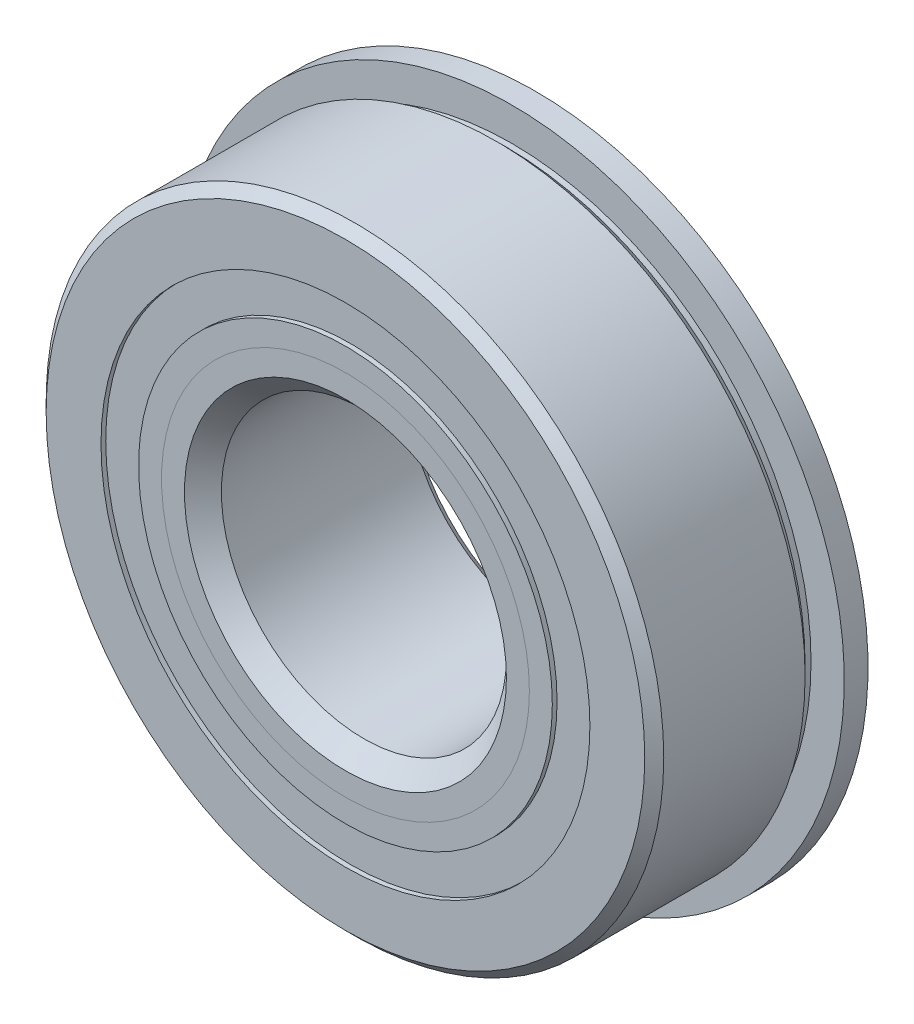
SolidWorks part; units mm, degrees
ref_plane "Front Plane" through (0, 0, 0) normal (0, 0, 1) x (1, 0, 0)
ref_plane "Top Plane" through (0, 0, 0) normal (0, 1, 0) x (1, 0, 0)
ref_plane "Right Plane" through (0, 0, 0) normal (1, 0, 0) x (0, 0, -1)
sketch "Sketch1" plane through (0, 0, 0) normal (1, 0, 0) x (0, 0, -1)
  line L0 (-6.35, 0) -> (6.35, 0) construction
  line L1 (0, 20.6375) -> (0, -20.6375) construction
  line L2 (5.715, 20.6375) -> (-5.715, 20.6375)
  line L3 (-5.715, 20.6375) -> (-6.35, 20.0025)
  line L4 (-6.35, 20.0025) -> (-6.35, 16.3373)
  line L5 (-6.35, 16.3373) -> (-2.8222, 16.3373)
  line L6 (6.35, 16.3373) -> (2.8222, 16.3373)
  line L7 (6.35, 20.0025) -> (6.35, 16.3373)
  line L8 (5.715, 20.6375) -> (6.35, 20.0025)
  line L9 (0, 20.6375) -> (0, 15.0813) construction
  line L10 (0, 15.0813) -> (0, 9.525) construction
  line L11 (6.35, 0) -> (7.9375, 0) construction
  arc A0 (-2.8222, 16.3373) -> (2.8222, 16.3373) centre (0, 15.0813) cw
  point P14 (0, 9.525)
  dimension "D3" = 5.6444
  dimension "D1" = 45
  dimension "Width" = 12.7
  dimension "OD" = 41.275
  dimension "D2" = 0.635
  dimension "Shaft Dia" = 19.05
  dimension "D4" = 1.256
  dimension "Total Wd" = 14.2875
revolve "Revolve1" add sketch "Sketch1" angle 360 about L0
sketch "Sketch2" plane through (0, 0, 0) normal (1, 0, 0) x (0, 0, -1)
  line L0 (-6.35, 13.8252) -> (-2.8222, 13.8252)
  line L1 (-6.35, 20.0025) -> (-6.35, -20.0025) construction
  line L2 (-6.35, 13.8252) -> (-6.35, 12.2919)
  line L3 (-6.35, 12.2919) -> (-4.8167, 10.7586)
  line L4 (-4.8167, 10.7586) -> (0, 10.7586)
  line L5 (0, 20.6375) -> (0, -20.6375) construction
  line L6 (0, 10.7586) -> (0, 11.9921)
  line L7 (0, 11.9921) -> (0, 9.525) construction
  line L8 (-6.35, 13.8252) -> (-6.35, 10.7586) construction
  line L9 (-6.35, 10.7586) -> (-4.8167, 10.7586) construction
  arc A0 (-2.8222, 13.8252) -> (0, 11.9921) centre (0, 15.0813) ccw
  arc A1 (2.8222, 16.3373) -> (-2.8222, 16.3373) centre (0, 15.0813) ccw construction
  circle A2 centre (0, 15.0813) radius 3.0891 construction
  dimension "D1" = 45
revolve "Revolve2" add sketch "Sketch2" angle 360 about L0
sketch "Sketch3" plane through (0, 0, 0) normal (1, 0, 0) x (0, 0, -1)
  line L0 (-6.35, 12.2919) -> (-4.8167, 10.7586)
  line L1 (-4.8167, 10.7586) -> (0, 10.7586)
  line L2 (0, 10.7586) -> (0, 11.9921)
  line L3 (-6.35, 12.2919) -> (-6.35, 10.7586)
  line L4 (-6.35, 13.8252) -> (-6.35, 10.7586) construction
  line L5 (-6.35, 10.7586) -> (-5.1164, 9.525)
  line L6 (-5.1164, 9.525) -> (7.3025, 9.525)
  line L8 (7.3025, 9.525) -> (7.9375, 10.16)
  line L10 (7.9375, 10.16) -> (7.9375, 13.8252)
  line L11 (7.9375, 13.8252) -> (2.8222, 13.8252)
  line L13 (5.715, 20.6375) -> (6.35, 20.0025) construction
  circle A0 centre (0, 15.0813) radius 3.0891 construction
  arc A1 (2.8222, 13.8252) -> (0, 11.9921) centre (0, 15.0813) cw
revolve "Revolve3" add sketch "Sketch3" angle 360 about L0
sketch "Sketch5" plane through (0, 0, 0) normal (1, 0, 0) x (0, 0, -1)
  line L0 (6.35, 20.0025) -> (6.35, 16.3373) construction
  line L1 (6.35, 18.1699) -> (4.7625, 18.1699)
  line L2 (6.35, 18.1699) -> (6.35, 22.225)
  line L3 (6.35, 22.225) -> (4.7625, 22.225)
  line L4 (4.7625, 18.1699) -> (4.7625, 22.225)
  line L5 (7.9375, 0) -> (-6.35, 0) construction
  dimension "D1" = 1.5875
  dimension "Flange OD" = 44.45
revolve "Revolve5" add sketch "Sketch5" angle 360 about L5
sketch "Sketch6" plane through (0, 0, 0) normal (1, 0, 0) x (0, 0, -1)
  line L0 (3.7306, 20.6375) -> (4.3656, 20.0025)
  line L1 (5.715, 20.6375) -> (-5.715, 20.6375) construction
  line L2 (4.3656, 20.0025) -> (4.7625, 20.0025)
  line L3 (4.7625, 20.0025) -> (4.7625, 20.6375)
  line L4 (4.7625, 20.6375) -> (3.7306, 20.6375)
  line L5 (5.715, 20.6375) -> (6.35, 20.0025) construction
  line L6 (4.7625, 18.1699) -> (4.7625, 22.225) construction
  dimension "D1" = 0.3969
revolve "Cut-Revolve1" cut sketch "Sketch6" angle 360 about L0
sketch "Sketch4" plane through (0, 0, 0) normal (1, 0, 0) x (0, 0, -1)
  line L0 (-3.0891, 15.0813) -> (3.0891, 15.0813)
  circle A1 centre (0, 15.0813) radius 3.0891 construction
  arc A2 (-3.0891, 15.0813) -> (3.0891, 15.0813) centre (0, 15.0813) cw
  arc A3 (2.8222, 16.3373) -> (-2.8222, 16.3373) centre (0, 15.0813) ccw construction
revolve "Revolve4" add sketch "Sketch4" angle 360 about L0
ref_axis "Axis1" through (0, 0, -6.35) along (0, 0, 1)
pattern_circular "CirPattern1" count 14 every 25.714 about axis through (0, 0, -6.35) along (0, 0, 1) of bodies 104
sketch "Sketch7" plane through (0, 0, 0) normal (1, 0, 0) x (0, 0, -1)
  line L0 (-6.35, 16.3373) -> (-2.8222, 16.3373) construction
  line L1 (-6.0325, 16.3373) -> (-3.0891, 16.3373)
  line L2 (-6.0325, 16.3373) -> (-6.0325, 13.8252)
  line L3 (-6.0325, 13.8252) -> (-3.0891, 13.8252)
  line L4 (-3.0891, 16.3373) -> (-3.0891, 13.8252)
  line L5 (-6.35, 13.8252) -> (-2.8222, 13.8252) construction
  line L6 (-5.715, 20.6375) -> (-6.35, 20.0025) construction
  line L7 (6.35, 16.3373) -> (2.8222, 16.3373) construction
  line L8 (6.0325, 16.3373) -> (3.0891, 16.3373)
  line L9 (6.0325, 16.3373) -> (6.0325, 13.8252)
  line L10 (6.0325, 13.8252) -> (3.0891, 13.8252)
  line L11 (3.0891, 16.3373) -> (3.0891, 13.8252)
  line L12 (7.9375, 13.8252) -> (2.8222, 13.8252) construction
  line L13 (5.715, 20.6375) -> (6.35, 20.0025) construction
  circle A0 centre (0, 15.0813) radius 3.0891 construction
  point P10 (-6.0325, 20.32)
  point P21 (6.0325, 20.32)
revolve "Revolve6" add sketch "Sketch7" angle 360 about L0
equation "\"D2@Sketch1\" = \"Width@Sketch1\"*.05"
equation "\"D3@Sketch1\" = \"Width@Sketch1\"/2.25"
equation "\"D4@Sketch1\" = (((\"OD@Sketch1\"-\"Width@Sketch1\")/2)/3.25)/3.5"
equation "\"D2@CirPattern1\" = 360/\"Balls@CirPattern1\""
